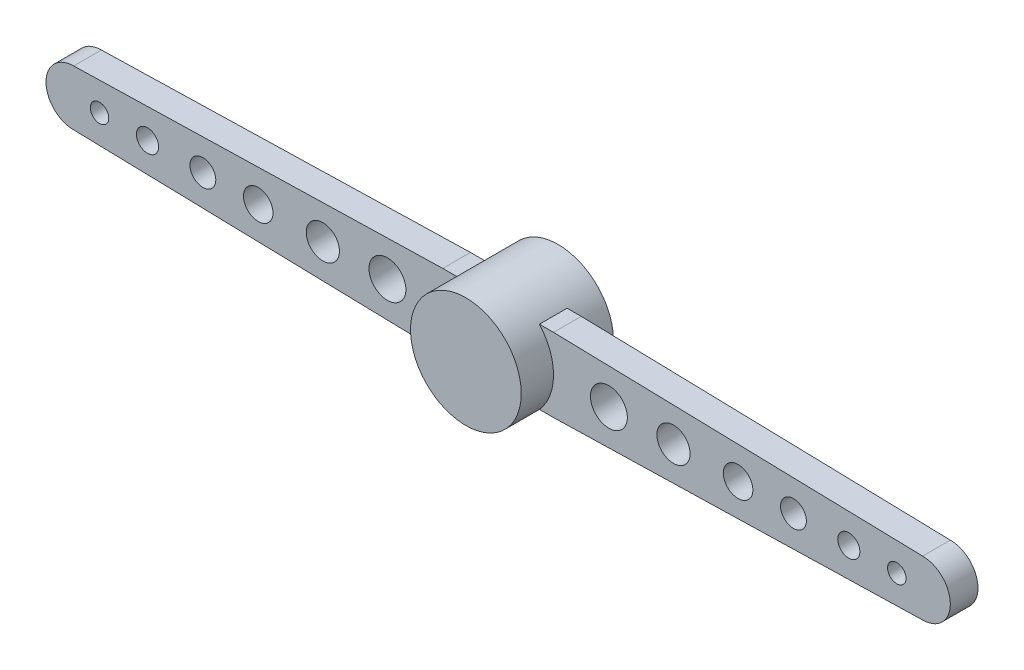
SolidWorks part; units mm, degrees
note: The reader was unsure of these and kept them because the rebuilt part matched: shared geometry of "Sketch1<3>".
ref_plane "Front Plane" through (0, 0, 0) normal (0, 0, 1) x (1, 0, 0)
ref_plane "Top Plane" through (0, 0, 0) normal (0, 1, 0) x (1, 0, 0)
ref_plane "Right Plane" through (0, 0, 0) normal (1, 0, 0) x (0, 0, -1)
sketch "Sketch1" plane through (0, 0, 0) normal (0, 0, 1) x (1, 0, 0)
  circle A0 centre (0, 0) radius 1.5
  circle A1 centre (0, 0) radius 1
  dimension "D1" = 2
  dimension "D2" = 3
extrude "Boss-Extrude1" add sketch "Sketch1" along normal blind 2.5 contours A0
extrude "Cut-Extrude1" cut sketch "Sketch1<3>" along normal blind 2 contours A1
sketch "Sketch1<3>" plane through (0, 0, 0) normal (0, 0, 1) x (1, 0, 0) same geometry as "Sketch1"
ref_plane "Plane1" through (-1.5, 0, 0) normal (-1, 0, 0) x (0, 0, 1)
sketch "Sketch2" plane through (-1.5, 0, 0) normal (-1, 0, 0) x (0, 0, 1)
  line L0 (0, 0) -> (2.5, 0) construction
  line L1 (2.5, -1.5) -> (2.5, 1.5) construction
  line L2 (1.25, 1.5) -> (1.25, -1.5) construction
  line L3 (2.5, 1.5) -> (0, 1.5) construction
  line L4 (0, -1.5) -> (2.5, -1.5) construction
  line L6 (1.625, -1) -> (0.875, -1)
  line L7 (1.625, -1) -> (1.625, 1)
  line L8 (1.625, 1) -> (0.875, 1)
  line L9 (0.875, -1) -> (0.875, 1)
  line L10 (1.625, -1) -> (0.875, 1) construction
  line L11 (1.625, 1) -> (0.875, -1) construction
  point P11 (1.25, 0)
  dimension "D1" = 2
  dimension "D2" = 0.75
ref_plane "Plane2" through (0, 0, 1.25) normal (0, 0, -1) x (0, -1, 0)
sketch "Sketch3" plane through (0, 0, 1.25) normal (0, 0, -1) x (0, -1, 0)
  line L0 (0, 1.5) -> (0, 11.5) construction
  line L1 (1, 1.5) -> (0.75, 11.5)
  line L2 (1, 1.5) -> (-1, 1.5) construction
  line L3 (1, 1.5) -> (-1, 1.5) construction
  line L4 (-1, 1.5) -> (-0.75, 11.5)
  line L5 (-1.5, 1.5) -> (1.5, 1.5) construction
  line L6 (-1, 1.5) -> (1, 1.5)
  line L7 (-1.65, 0) -> (1.65, 0) construction
  line L8 (0, -1.5) -> (0, -11.5) construction
  line L9 (-1, -1.5) -> (-0.75, -11.5)
  line L10 (1, -1.5) -> (0.75, -11.5)
  line L11 (-1, -1.5) -> (1, -1.5)
  arc A0 (0.75, 11.5) -> (-0.75, 11.5) centre (0, 11.5) ccw
  arc A1 (0.75, -11.5) -> (-0.75, -11.5) centre (0, -11.5) cw
  dimension "D2" = 0.75
  dimension "D1" = 10
  dimension "D3" = 0.25
  dimension "D4" = 0.25
extrude "Boss-Extrude2" add sketch "Sketch3" along normal blind 0.375 and the other way blind 0.375 separate body
extrude "Boss-Extrude3" add sketch "Sketch2" against normal up to surface (0.382 mm away)
ref_plane "Plane3" through (1.5, 0, 0) normal (-1, 0, 0) x (0, 0, 1)
sketch "Sketch4" plane through (1.5, 0, 0) normal (-1, 0, 0) x (0, 0, 1)
  line L0 (1.25, 1.65) -> (1.25, -1.65) construction
  line L1 (0.875, 1) -> (1.625, 1)
  line L2 (0.875, 1) -> (0.875, -1)
  line L3 (0.875, -1) -> (1.625, -1)
  line L4 (1.625, 1) -> (1.625, -1)
  line L5 (0.875, 1) -> (1.625, -1) construction
  line L6 (0.875, -1) -> (1.625, 1) construction
  point P0 (1.25, 0)
  dimension "D1" = 2
extrude "Boss-Extrude4" add sketch "Sketch4" along normal up to surface
ref_plane "Plane4" through (0, 0, 1.625) normal (0, 0, 1) x (1, 0, 0)
sketch "Sketch5" plane through (0, 0, 1.625) normal (0, 0, 1) x (1, 0, 0)
  line L0 (-12.25, 0) -> (12.25, 0) construction
  line L1 (0, -1.375) -> (0, 1.375) construction
  line L2 (0, 1.5) -> (0, -1.5) construction
  circle A0 centre (-10.8, 0) radius 0.25
  circle A1 centre (-9.5, 0) radius 0.3
  circle A2 centre (-8, 0) radius 0.35
  circle A3 centre (-6.5, 0) radius 0.4
  circle A4 centre (-4.75, 0) radius 0.45
  circle A5 centre (-3, 0) radius 0.5
  arc A7 (-11.5, 0.75) -> (-11.5, -0.75) centre (-11.5, 0) ccw construction
  arc A8 (11.5, -0.75) -> (11.5, 0.75) centre (11.5, 0) ccw construction
  circle A9 centre (3, 0) radius 0.5
  circle A10 centre (4.75, 0) radius 0.45
  circle A11 centre (6.5, 0) radius 0.4
  circle A12 centre (8, 0) radius 0.35
  circle A13 centre (9.5, 0) radius 0.3
  circle A14 centre (10.8, 0) radius 0.25
  circle A15 centre (0, 0) radius 1.5 construction
  dimension "D1" = 0.5
  dimension "D2" = 0.6
  dimension "D3" = 0.7
  dimension "D4" = 0.8
  dimension "D5" = 0.9
  dimension "D6" = 1
  dimension "D7" = 3
  dimension "D8" = 1.75
  dimension "D9" = 1.75
  dimension "D10" = 1.5
  dimension "D11" = 1.5
  dimension "D12" = 1.3
extrude "Cut-Extrude2" cut sketch "Sketch5" against normal up to next
